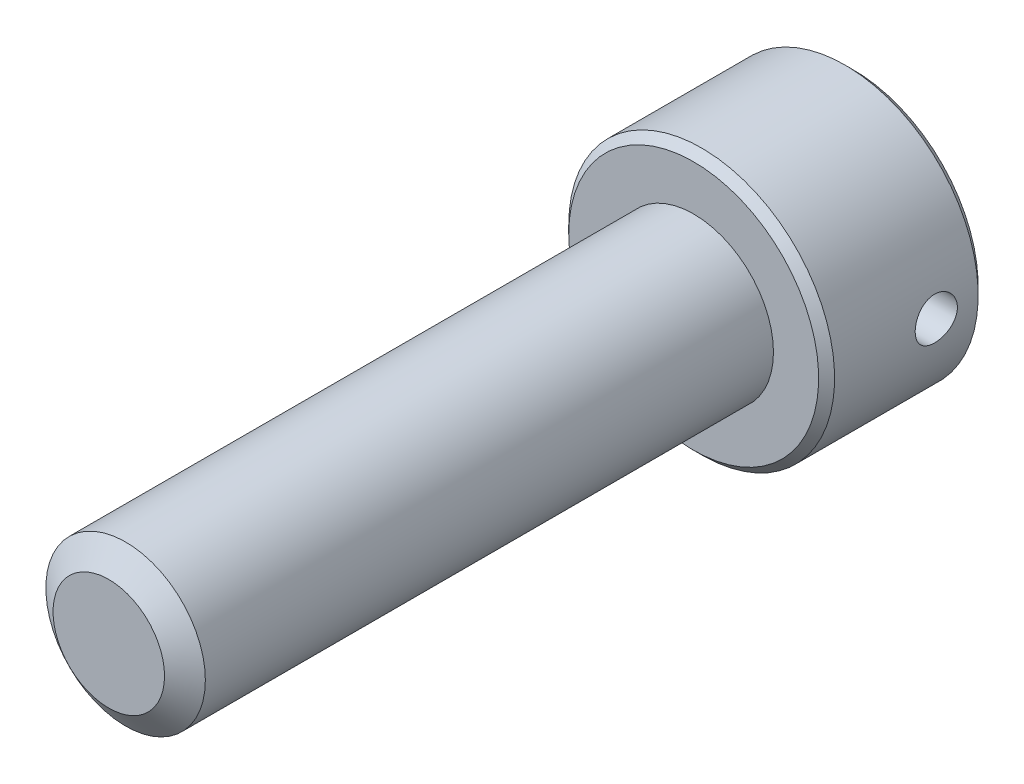
SolidWorks part; units mm, degrees
material "Alloy Steel"
ref_plane "Front Plane" through (0, 0, 0) normal (0, 0, 1) x (1, 0, 0)
ref_plane "Top Plane" through (0, 0, 0) normal (0, 1, 0) x (1, 0, 0)
ref_plane "Right Plane" through (0, 0, 0) normal (1, 0, 0) x (0, 0, -1)
sketch "Sketch1" plane through (0, 0, 0) normal (0, 0, 1) x (1, 0, 0)
  circle A0 centre (0, 0) radius 3
  dimension "OD" = 6
extrude "Extrude1" add sketch "Sketch1" against normal blind 22
sketch "Sketch2" plane through (0, 0, 0) normal (0, 0, 1) x (1, 0, 0)
  circle A0 centre (0, 0) radius 3 construction
  circle A1 centre (0, 0) radius 3
curve "Helix/Spiral1" pitch 1 height 23 turns 23 parameters "pitch"=1
sketch "Sketch3" plane through (0, 0, 0) normal (1, 0, 0) x (0, 0, -1)
  line L0 (-0.875, 3) -> (-0.5, 2.3505)
  line L1 (-0.5, 2.3505) -> (-0.375, 2.3505)
  line L2 (-0.375, 2.3505) -> (0, 3)
  line L3 (-0.875, 3) -> (0, 3)
  line L4 (-0.4375, 3) -> (-0.4375, 2.3505) construction
  line L5 (-0.6875, 2.6752) -> (-0.1875, 2.6752) construction
  line L6 (0, 3) -> (0, -3) construction
  line L7 (0, -3) -> (22, -3) construction
  point P11 (4.5, -3)
  dimension "D1" = 0.125
  dimension "D2" = 0.5
  dimension "D3" = 60
  dimension "D4" = 4.5
sweep "Cut-Sweep1" [suppressed] cut profiles "Sketch3" path "Helix/Spiral1"
sketch "Sketch4" plane through (0, 0, 0) normal (1, 0, 0) x (0, 0, -1)
  line L0 (0.6327, 3) -> (0, 2.0965)
  line L1 (0, 2.0965) -> (0, 3)
  line L2 (0.6327, 3) -> (0, 3)
  line L3 (-0.875, 3) -> (0, 3) construction
  line L4 (0, 0) -> (7.0209, 0) construction
  dimension "D1" = 55
  dimension "D2" = 0.254
revolve "Cut-Revolve1" cut sketch "Sketch4" angle 360 about L4
sketch "Sketch5" [suppressed] plane through (0, 0, 0) normal (1, 0, 0) x (0, 0, -1)
  line L0 (22, -2.3644) -> (22, 2.1406) construction
  line L1 (22, 3) -> (0.1203, 3)
  line L2 (22, 3) -> (22, 0)
  line L3 (22, 0) -> (0.0001, 0)
  line L4 (0.0001, 2.6698) -> (0.0001, 0)
  line L5 (0.1203, 3) -> (0.0001, 2.6698)
  line L6 (0, 0) -> (9.9695, 0) construction
  point P3 (0.0001, 3)
  point P10 (0.0001, 3)
  dimension "D1" = 0.3302
  dimension "Thread min" = 0.0001
  dimension "D3" = 20
revolve "partially thread" [suppressed] add sketch "Sketch5" angle 360 about L6
sketch "Sketch6" plane through (0, 0, -22) normal (0, 0, -1) x (-1, 0, 0)
  circle A0 centre (0, 0) radius 5
  dimension "head dia" = 10
extrude "Extrude2" add sketch "Sketch6" along normal blind 6
sketch "Sketch7" plane through (0, 0, -28) normal (0, 0, -1) x (-1, 0, 0)
  line L1 (0, 2.8868) -> (-2.5, 1.4434)
  line L2 (-2.5, 1.4434) -> (-2.5, -1.4434)
  line L3 (-2.5, -1.4434) -> (0, -2.8868)
  line L4 (0, -2.8868) -> (2.5, -1.4434)
  line L5 (2.5, -1.4434) -> (2.5, 1.4434)
  line L6 (2.5, 1.4434) -> (0, 2.8868)
  circle A0 centre (0, 0) radius 2.5 construction
  dimension "hex dia" = 5
extrude "Cut-Extrude1" cut sketch "Sketch7" against normal blind 3.75
sketch "Sketch8" plane through (0, 0, -28) normal (0, 0, -1) x (-1, 0, 0)
  circle A0 centre (0, 0) radius 2.8868
extrude "Cut-Extrude2" cut sketch "Sketch8" against normal through all draft 45
chamfer "Chamfer1" distance 0.3 angle 45 2 edges at (-5, 0, -28) (-5, 0, -22)
sketch "Sketch9" plane through (0, 0, 0) normal (1, 0, 0) x (0, 0, -1)
  line L0 (0, 3) -> (0, -3) construction
  line L1 (5.5, 3) -> (5.5, -3) construction
  dimension "D1" = 5.5
sketch "Sketch10" plane through (0, 0, 0) normal (1, 0, 0) x (0, 0, -1)
  line L0 (22, 3) -> (22, 0)
  line L1 (22, 3) -> (21.75, 3)
  line L2 (21.75, 3) -> (20.5074, 0)
  line L3 (22, 0) -> (20.5074, 0)
  line L4 (22, 4.7) -> (22, -4.7) construction
  dimension "D1" = 22.5
  dimension "D2" = 0.25
revolve "Revolve1" add sketch "Sketch10" angle 360 about L3
sketch "Sketch13" plane through (0, 0, 0) normal (1, 0, 0) x (0, 0, -1)
  line L0 (28, -1.4434) -> (28, 1.4434) construction
  line L1 (24.25, -1.4434) -> (24.25, 1.4434) construction
  line L2 (28, -1.4434) -> (28, 1.4434) construction
  line L3 (24.25, -1.4434) -> (24.25, 1.4434) construction
  line L4 (24.25, 0) -> (28, 0) construction
  circle A0 centre (26.125, 0) radius 0.7937
  dimension "D1" = 1.5875
extrude "Cut-Extrude4" cut sketch "Sketch13" against normal through all both and the other way through all
equation "\"D3@Helix/Spiral1\" = \"screw length@Extrude1\"+\"pitch@Helix/Spiral1\""
equation "\"D1@Sketch3\" = \"pitch@Helix/Spiral1\"*.125"
equation "\"D2@Sketch3\" = \"pitch@Helix/Spiral1\"*.5"
equation "\"D1@Cut-Extrude1\" = \"hex dia@Sketch7\"*.75"
equation "\"D1@Chamfer1\" = \"head dia@Sketch6\"*.03"
equation "\"D1@Sketch9\" = \"pitch@Helix/Spiral1\"*5.5"
equation "\"D2@Sketch10\" = \"pitch@Helix/Spiral1\"*.25"
equation "\"D4@Sketch3\" = \"pitch@Helix/Spiral1\"*4.50"
